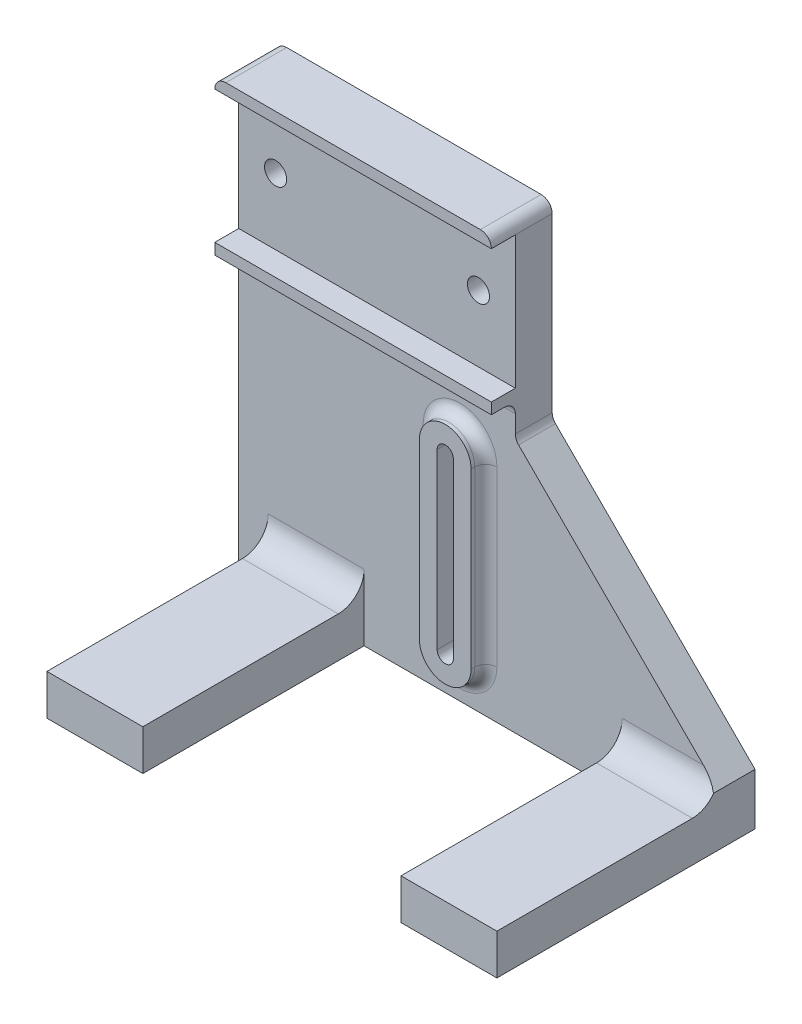
SolidWorks part; units mm, degrees
material "PET"
ref_plane "Front Plane" through (0, 0, 0) normal (0, 0, 1) x (1, 0, 0)
ref_plane "Top Plane" through (0, 0, 0) normal (0, 1, 0) x (1, 0, 0)
ref_plane "Right Plane" through (0, 0, 0) normal (1, 0, 0) x (0, 0, -1)
sketch "Sketch2" plane through (0, 0, 0) normal (0, 0, 1) x (1, 0, 0)
  line L0 (0, 0) -> (130, 0)
  line L1 (130, 0) -> (130, 14)
  line L2 (130, 14) -> (75, 69)
  line L3 (75, 69) -> (75, 120)
  line L4 (75, 120) -> (0, 120)
  line L5 (0, 120) -> (0, 0)
  dimension "D1" = 120
  dimension "D2" = 75
  dimension "D3" = 14
  dimension "D4" = 55
  dimension "D5" = 130
extrude "Boss-Extrude1" add sketch "Sketch2" against normal blind 10
sketch "Sketch3" plane through (0, 0, 0) normal (0, 0, 1) x (1, 0, 0)
  line L0 (75, 69) -> (75, 120) construction
  line L1 (0, 120) -> (75, 120)
  line L2 (0, 120) -> (0, 117)
  line L3 (0, 117) -> (75, 117)
  line L4 (75, 120) -> (75, 117)
  line L5 (0, 120) -> (75, 117) construction
  line L6 (0, 117) -> (75, 120) construction
  line L7 (0, 120) -> (0, 0) construction
  line L8 (0, 81) -> (75, 81)
  line L9 (0, 81) -> (0, 78)
  line L10 (0, 78) -> (75, 78)
  line L11 (75, 81) -> (75, 78)
  line L12 (0, 81) -> (75, 78) construction
  line L13 (0, 78) -> (75, 81) construction
  point P4 (37.5, 118.5)
  point P12 (37.5, 79.5)
  dimension "D1" = 3
  dimension "D2" = 36
extrude "Boss-Extrude2" add sketch "Sketch3" along normal blind 6.5
sketch "Sketch4" plane through (0, 0, 0) normal (0, 0, 1) x (1, 0, 0)
  line L0 (0, 99) -> (75, 99) construction
  line L1 (0, 117) -> (0, 81) construction
  line L2 (75, 81) -> (75, 117) construction
  circle A0 centre (10, 99) radius 3
  circle A1 centre (65, 99) radius 3
  dimension "D1" = 10
  dimension "D3" = 6
  dimension "D2" = 10
extrude "Cut-Extrude2" cut sketch "Sketch4" against normal up to surface (10 mm away) up to face at (68.3333, 53.8333, -10)
sketch "Sketch5" plane through (0, 0, 0) normal (0, 0, 1) x (1, 0, 0)
  line L0 (0, 0) -> (130, 0) construction
  line L1 (130, 11) -> (104, 11)
  line L2 (130, 11) -> (130, 0)
  line L3 (130, 0) -> (104, 0)
  line L4 (104, 11) -> (104, 0)
  line L5 (130, 11) -> (104, 0) construction
  line L6 (130, 0) -> (104, 11) construction
  line L7 (69, 0) -> (69, 120) construction
  line L8 (75, 120) -> (0, 120) construction
  line L9 (8, 0) -> (34, 0)
  line L10 (34, 11) -> (34, 0)
  line L11 (8, 11) -> (34, 11)
  line L12 (8, 11) -> (8, 0)
  line L13 (0, 78) -> (0, 0) construction
  point P4 (117, 5.5)
  point P18 (64.0042, 120)
  point P19 (69, 120)
  point P20 (69, -6.2012)
  dimension "D1" = 26
  dimension "D2" = 8
  dimension "D3" = 3
extrude "Boss-Extrude3" add sketch "Sketch5" along normal blind 60
sketch "Sketch6" plane through (0, 0, 0) normal (0, 0, 1) x (1, 0, 0)
  line L0 (0, 16) -> (6, 16) construction
  line L1 (0, 78) -> (0, 0) construction
  line L2 (0, 13) -> (6, 7)
  line L3 (6, 7) -> (6, 25)
  line L4 (6, 25) -> (0, 19)
  line L5 (8, 0) -> (34, 0) construction
  line L6 (0, 19) -> (0, 13)
  line L7 (0, 36) -> (-23.6105, 36) construction
  line L8 (0, 56) -> (6, 56) construction
  line L9 (6, 47) -> (0, 53)
  line L10 (6, 65) -> (6, 47)
  line L11 (0, 59) -> (6, 65)
  line L12 (0, 53) -> (0, 59)
  dimension "D1" = 6
  dimension "D2" = 6
  dimension "D3" = 16
  dimension "D4" = 6
  dimension "D5" = 40
sketch "Sketch7" plane through (0, 0, 0) normal (0, 0, 1) x (1, 0, 0)
  line L0 (60, 0) -> (60, 120) construction
  line L1 (34, 0) -> (104, 0) construction
  line L2 (75, 120) -> (0, 120) construction
  line L3 (60, 13) -> (60, 60) construction
  line L4 (53, 13) -> (53, 60)
  line L5 (67, 13) -> (67, 60)
  arc A0 (53, 13) -> (67, 13) centre (60, 13) ccw
  arc A1 (67, 60) -> (53, 60) centre (60, 60) ccw
  point P4 (60, 36.5)
  point P14 (60, 6)
  point P15 (60, 67)
  dimension "D1" = 26
  dimension "D2" = 7
  dimension "D3" = 6
extrude "Boss-Extrude5" add sketch "Sketch7" along normal blind 4
sketch "Sketch8" plane through (0, 0, 4) normal (0, 0, 1) x (1, 0, 0)
  line L4 (62.2, 13) -> (62.2, 60)
  line L5 (57.8, 60) -> (57.8, 13)
  line L6 (62.2, 13) -> (62.2, 60)
  line L7 (57.8, 60) -> (57.8, 13)
  arc A4 (57.8, 13) -> (62.2, 13) centre (60, 13) ccw
  arc A5 (62.2, 60) -> (57.8, 60) centre (60, 60) ccw
  arc A6 (57.8, 13) -> (62.2, 13) centre (60, 13) ccw
  arc A7 (62.2, 60) -> (57.8, 60) centre (60, 60) ccw
  dimension "D1" = 4.8
extrude "Cut-Extrude3" cut sketch "Sketch8" against normal through all
fillet "Fillet2" radius 3 4 edges at (75, 120, -1.75) (0, 120, -1.75) (37.5, 78, 0) (75, 69, -5)
extrude "Cut-Extrude4" [suppressed] cut sketch "Sketch6" against normal through all
fillet "Fillet3" [suppressed] radius 1.25
sketch "Sketch9" plane through (0, 0, -10) normal (0, 0, -1) x (-1, 0, 0)
  line L4 (-64, 60) -> (-64, 13)
  line L5 (-56, 13) -> (-56, 60)
  line L6 (-64, 60) -> (-64, 13)
  line L7 (-56, 13) -> (-56, 60)
  arc A4 (-64, 13) -> (-56, 13) centre (-60, 13) ccw
  arc A5 (-56, 60) -> (-64, 60) centre (-60, 60) ccw
  arc A6 (-64, 13) -> (-56, 13) centre (-60, 13) ccw
  arc A7 (-56, 60) -> (-64, 60) centre (-60, 60) ccw
  dimension "D1" = 1.8
extrude "Cut-Extrude5" cut sketch "Sketch9" against normal offset from surface (7.75 mm away) 6.25 up to face at (60, 36.5, 4)
fillet "Fillet4" radius 3 4 edges at (60, 67, 0) (67, 36.5, 0) (60, 6, 0) (53, 36.5, 0)
fillet "Fillet5" radius 7 2 edges at (117, 11, 0) (21, 11, 0)
